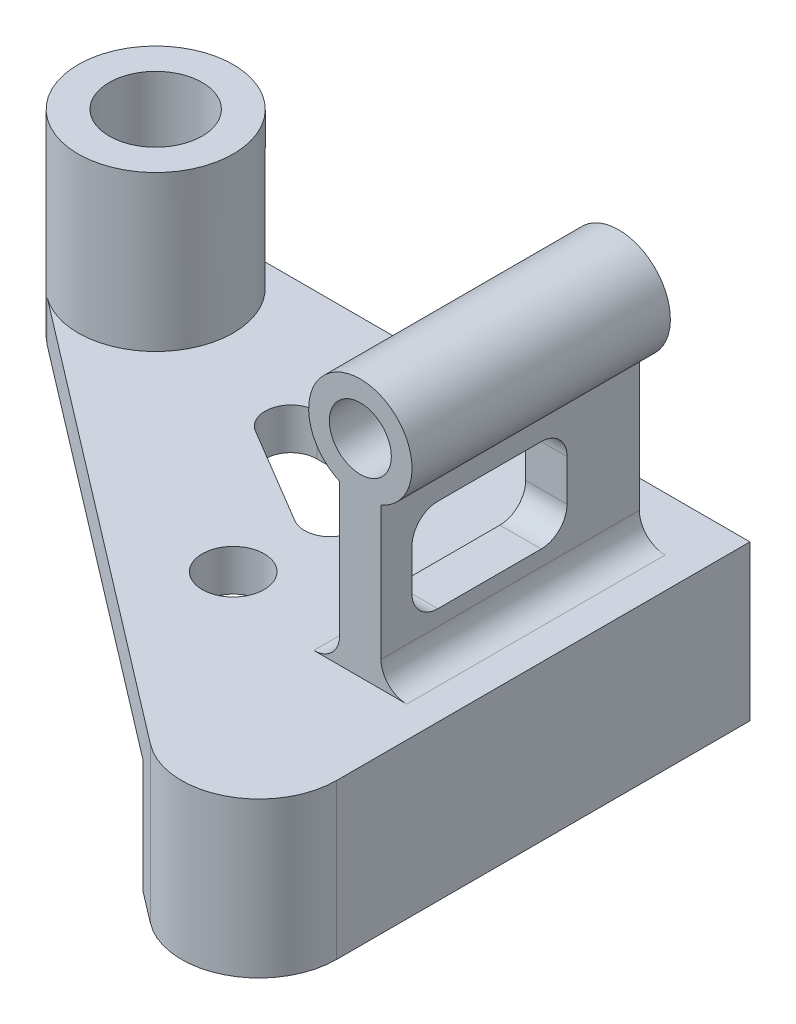
SolidWorks part; units mm, degrees
other "DetailItem1"
ref_plane "Front Plane" through (0, 0, 0) normal (0, 0, 1) x (1, 0, 0)
ref_plane "Top Plane" through (0, 0, 0) normal (0, 1, 0) x (1, 0, 0)
ref_plane "Right Plane" through (0, 0, 0) normal (1, 0, 0) x (0, 0, -1)
sketch "Sketch1" plane through (0, 0, 0) normal (0, 1, 0) x (1, 0, 0)
  line L0 (0, 0) -> (-100, 0)
  line L1 (0, 0) -> (0, -80)
  line L2 (-63.8245, -20) -> (-45, -20)
  line L3 (-24.1118, -91.9154) -> (-109.1118, -26.9154)
  line L4 (-25, -10.3952) -> (-5, -10.3952)
  line L5 (-25, -10.3952) -> (-25, -60.3952)
  line L6 (-25, -60.3952) -> (-5, -60.3952)
  line L7 (-5, -10.3952) -> (-5, -60.3952)
  line L8 (-47.5574, -40.5015) -> (-66.3819, -29.2965)
  line L9 (-40, -25) -> (-40, -36.2051)
  line L10 (-15, -10.3952) -> (-15, -60.3952) construction
  circle A0 centre (-100, -15) radius 15
  arc A1 (-24.1118, -91.9154) -> (0, -80) centre (-15, -80) ccw
  circle A2 centre (-100, -15) radius 9
  circle A4 centre (-45, -10) radius 6
  circle A5 centre (-45, -55) radius 6
  arc A6 (-63.8245, -20) -> (-66.3819, -29.2965) centre (-63.8245, -25) ccw
  arc A7 (-40, -25) -> (-45, -20) centre (-45, -25) ccw
  arc A8 (-40, -36.2051) -> (-47.5574, -40.5015) centre (-45, -36.2051) cw
  point P29 (-82, -20)
  point P32 (-40, -20)
  point P35 (-40, -45)
  dimension "D1" = 30
  dimension "D2" = 18
  dimension "D3" = 30
  dimension "D7" = 12
  dimension "D16" = 5
  dimension "D17" = 5
  dimension "D18" = 5
  dimension "D4" = 100
  dimension "D5" = 80
  dimension "D6" = 50
  dimension "D8" = 10
  dimension "D9" = 20
  dimension "D10" = 25
  dimension "D11" = 45
  dimension "D12" = 40
  dimension "D13" = 42
  dimension "D14" = 45
  dimension "D15" = 15
  dimension "D19" = 20
extrude "Boss-Extrude2" add sketch "Sketch1" against normal blind 30 contours L10 L4 L5 L6 | L4 L10 L6 L7 | A0 A2 | L3 A1 L1 L0 A0 A5 A4 L4 L7 L6 L5 L9 A8 L8 A6 L2 A7 region at (-1.4467, 0, 40) region at (-89.6934, 0, 4.6934) region at (-20, 0, 35.3952) region at (-10, 0, 35.3952)
sketch "Sketch2" plane through (0, 0, 0) normal (0, 0, -1) x (-1, 0, 0)
  line L0 (0, -30) -> (0, 0) construction
  line L1 (30, -8) -> (142.9506, -8)
  line L2 (30, -8) -> (30, -46.7444)
  line L3 (30, -46.7444) -> (142.9506, -46.7444)
  line L4 (142.9506, -8) -> (142.9506, -46.7444)
  line L5 (0, 0) -> (100, 0) construction
  dimension "D1" = 30
  dimension "D2" = 8
extrude "Cut-Extrude1" cut sketch "Sketch2" against normal through all
extrude "Boss-Extrude3" add sketch "Sketch1<3>" along normal blind 30 contours A0 A2 region at (-89.6934, 0, 4.6934)
sketch "Sketch1<3>" plane through (0, 0, 0) normal (0, 1, 0) x (1, 0, 0) same geometry as "Sketch1"
extrude "Boss-Extrude4" add sketch "Sketch1<4>" along normal blind 50 contours L7 L4 L5 L6 | L5 L4 L7 L6 region at (-15, 0, 35.3952)
sketch "Sketch1<4>" plane through (0, 0, 0) normal (0, 1, 0) x (1, 0, 0) same geometry as "Sketch1"
sketch "Sketch3" plane through (0, 0, 60.3952) normal (0, 0, 1) x (1, 0, 0)
  line L2 (-25, 50) -> (-25, 0) construction
  line L3 (-25, 50) -> (-5, 50)
  line L4 (-25, 50) -> (-25, 0)
  line L5 (-25, 0) -> (-5, 0)
  line L6 (-5, 50) -> (-5, 0)
  line L7 (-19, 30.8348) -> (-19, 0)
  line L8 (-11, 0) -> (-11, 30.8348)
  line L9 (-25, 50) -> (-5, 50) construction
  circle A2 centre (-15, 40) radius 10
  circle A3 centre (-15, 40) radius 6
  line M9 (-25, 0) -> (-5, 0)
  line M10 (-5, 0) -> (-5, 50)
  line M11 (-5, 50) -> (-25, 50)
  line M12 (-25, 50) -> (-25, 0)
  dimension "D1" = 20
  dimension "D2" = 12
  dimension "D3" = 10
  dimension "D4" = 8
  dimension "D5" = 10
extrude "Cut-Extrude2" cut sketch "Sketch3" against normal through all contours A2 L4 L7 M9 | A2 L8 M9 M10 | A2 L6 M11 | A2 L3 M12 | A3 region at (-22.7663, 47.7663, 60.3952) region at (-7.2337, 47.7663, 60.3952) region at (-22.1039, 16.7626, 60.3952) region at (-7.8961, 16.7626, 60.3952) region at (-15, 40, 60.3952)
fillet "Fillet1" radius 5 2 edges at (-11, 0, 35.3952) (-19, 0, 35.3952)
sketch "Sketch4" plane through (-11, 0, 0) normal (1, 0, 0) x (0, 0, -1)
  line L0 (-60.3952, 5) -> (-60.3952, 30.8348) construction
  line L1 (-49.3952, 26) -> (-29.3952, 26)
  line L2 (-54.3952, 21) -> (-54.3952, 13)
  line L3 (-49.3952, 8) -> (-29.3952, 8)
  line L4 (-24.3952, 21) -> (-24.3952, 13)
  line L6 (-10.3952, 0) -> (-60.3952, 0) construction
  arc A0 (-29.3952, 26) -> (-24.3952, 21) centre (-29.3952, 21) cw
  arc A1 (-29.3952, 8) -> (-24.3952, 13) centre (-29.3952, 13) ccw
  arc A2 (-54.3952, 13) -> (-49.3952, 8) centre (-49.3952, 13) ccw
  arc A3 (-49.3952, 26) -> (-54.3952, 21) centre (-49.3952, 21) ccw
  point P6 (-24.3952, 17)
  dimension "D4" = 5
  dimension "D1" = 6
  dimension "D2" = 18
  dimension "D3" = 30
  dimension "D5" = 8
extrude "Cut-Extrude3" cut sketch "Sketch4" against normal up to surface (8 mm away) up to face at (-19, 17.9174, 35.3952)
